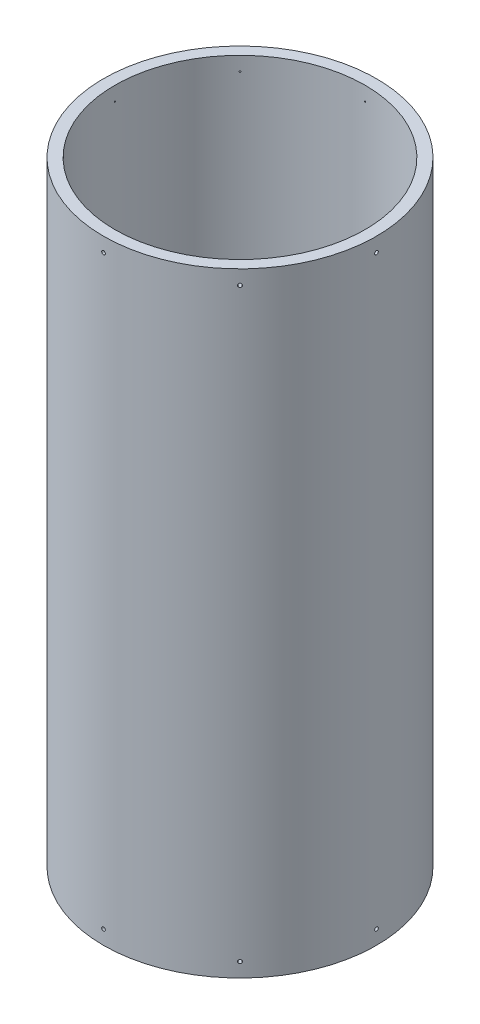
SolidWorks part; units mm, degrees
ref_plane "Front Plane" through (0, 0, 0) normal (0, 0, 1) x (1, 0, 0)
ref_plane "Top Plane" through (0, 0, 0) normal (0, 1, 0) x (1, 0, 0)
ref_plane "Right Plane" through (0, 0, 0) normal (1, 0, 0) x (0, 0, -1)
sketch "Sketch1" plane through (0, 0, 0) normal (0, 1, 0) x (1, 0, 0)
  circle A0 centre (0, 0) radius 139.7
  circle A1 centre (0, 0) radius 152.4
  dimension "D1" = 279.4
  dimension "D2" = 304.8
extrude "Boss-Extrude1" add sketch "Sketch1" along normal blind 685.8
ref_plane "Plane1" through (0, 0, 152.4) normal (0, 0, 1) x (1, 0, 0)
ref_plane "Plane2" through (-152.4, 0, 0) normal (-1, 0, 0) x (0, 0, 1)
hole_wizard "#10-32 Tapped Hole1" positions "Sketch2" profile "Sketch3" tap size "#10-32" standard "ANSI Inch"
sketch "Sketch2" plane through (0, 0, 152.4) normal (0, 0, 1) x (1, 0, 0)
  line L0 (0, 669.925) -> (0, 15.875)
  line L1 (0, 15.875) -> (0, 0)
  line L3 (152.4, 685.8) -> (-152.4, 685.8) construction
  line L4 (-152.4, 0) -> (152.4, 0) construction
  point P0 (0, 669.925)
  point P2 (0, 15.875)
  dimension "D1" = 15.875
  dimension "D2" = 15.875
sketch "Sketch3" plane through (0, 669.925, 152.4) normal (1, 0, 0) x (0, -1, 0)
  line L0 (0, 0) -> (0, 13.1513)
  line L1 (0, 13.1513) -> (2.0193, 11.938)
  line L2 (2.0193, 11.938) -> (2.0193, 0)
  line L5 (2.0193, 0) -> (0, 0)
  line L10 (0, 13.1513) -> (-2.0193, 11.938) construction
  line L11 (0, -6.35) -> (0, 107.95) construction
  dimension "Tap Drill Dia." = 4.0386
  dimension "Tap Drill Depth" = 11.938
  dimension "Drill Angle" = 118
cosmetic thread "Hole Thread1" parameters "D1"=9.652, "D2"=4.826
cosmetic thread "Hole Thread2" parameters "D1"=9.652, "D2"=4.826
pattern_circular "CirPattern1" count 8 over 360 about axis through (0, 0, 0) along (0, 1, 0) of "#10-32 Tapped Hole1"
hole_wizard "Hole1" positions "Sketch4" profile "Sketch6" legacy end condition up to next
sketch "Sketch4" plane through (-152.4, 0, 0) normal (1, 0, 0) x (0, 0, -1)
  line L0 (0, 104.775) -> (0, 0)
  point P0 (0, 104.775)
  dimension "D1" = 104.775
sketch "Sketch6" plane through (-152.4, 104.775, 0) normal (0, 1, 0) x (0, 0, 1)
  line L0 (0, 0) -> (0, 12.7)
  line L1 (0, 12.7) -> (22.225, 12.7)
  line L2 (22.225, 12.7) -> (22.225, 0)
  line L3 (22.225, 0) -> (0, 0)
  line L4 (0, 110) -> (0, -10) construction
  dimension "Diameter" = 44.45
  dimension "Depth" = 12.7
